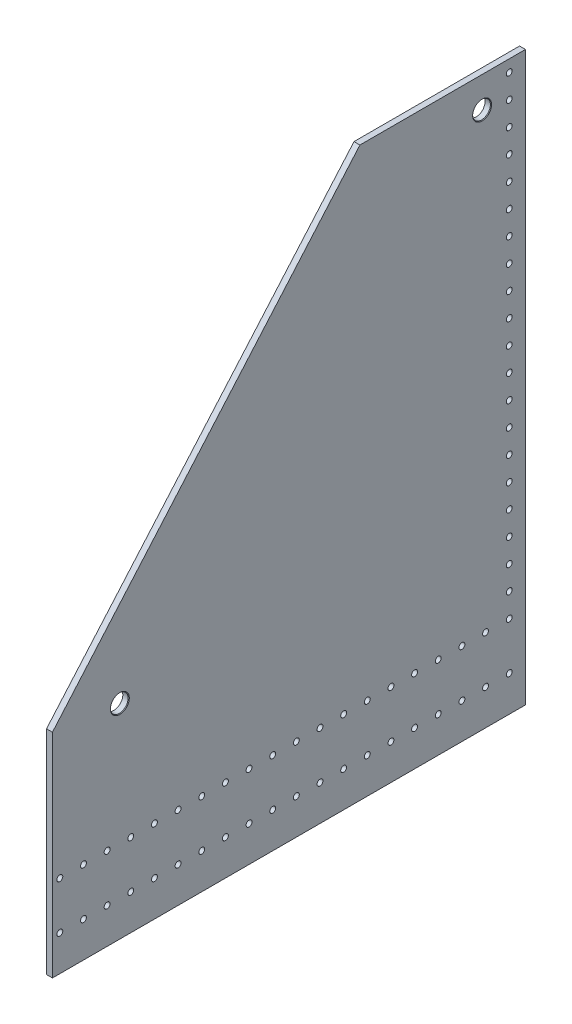
SolidWorks part; units mm, degrees
ref_plane "Front Plane" through (0, 0, 0) normal (0, 0, 1) x (1, 0, 0)
ref_plane "Top Plane" through (0, 0, 0) normal (0, 1, 0) x (1, 0, 0)
ref_plane "Right Plane" through (0, 0, 0) normal (1, 0, 0) x (0, 0, -1)
sketch "Sketch1" plane through (0, 0, 0) normal (1, 0, 0) x (0, 0, -1)
  line L1 (-86.4742, 48.8926) -> (421.5258, 48.8926)
  line L2 (-86.4742, 48.8926) -> (-86.4742, -560.7074)
  line L3 (-86.4742, -560.7074) -> (421.5258, -560.7074)
  line L4 (421.5258, 48.8926) -> (421.5258, -560.7074)
  dimension "D1" = 609.6
  dimension "D2" = 508
extrude "Boss-Extrude1" add sketch "Sketch1" along normal blind 6.35
sketch "Sketch4" plane through (6.35, 0, 0) normal (1, 0, 0) x (0, 0, -1)
  line L0 (-86.4742, 48.8926) -> (243.7258, 48.8926)
  line L1 (421.5258, 48.8926) -> (-86.4742, 48.8926) construction
  line L2 (243.7258, 48.8926) -> (-86.4742, -332.1074)
  line L3 (-86.4742, 48.8926) -> (-86.4742, -560.7074) construction
  line L4 (-86.4742, -332.1074) -> (-86.4742, 48.8926)
  dimension "D1" = 330.2
  dimension "D2" = 381
extrude "Cut-Extrude1" cut sketch "Sketch4" against normal blind 6.35
hole_wizard "3/4 (0.75) Diameter Hole1" positions "Sketch5" profile "Sketch6" hole size "3/4" standard "ANSI Inch" end condition through all
sketch "Sketch5" plane through (6.35, 0, 0) normal (1, 0, 0) x (0, 0, -1)
  point P0 (-14.0842, -341.6324)
  point P3 (374.9536, 15.7883)
sketch "Sketch6" plane through (6.35, -341.6324, 14.0842) normal (0, 1, 0) x (0, 0, -1)
  line L0 (0, 0) -> (0, 6.35)
  line L1 (0, 6.35) -> (9.525, 6.35)
  line L2 (9.525, 6.35) -> (9.525, 0.635)
  line L3 (9.525, 0.635) -> (10.16, 0)
  line L5 (10.16, 0) -> (0, 0)
  line L6 (-9.525, 0.635) -> (-10.16, 0) construction
  line L11 (0, -6.35) -> (0, 107.95) construction
  dimension "Thru Hole Dia." = 19.05
  dimension "Thru Hole Depth" = 6.35
  dimension "Near C'Sink Dia." = 20.32
  dimension "Near C'Sink Angle" = 90
hole_wizard "1/4 (0.25) Diameter Hole1" positions "Sketch7" profile "Sketch9" hole size "1/4" standard "ANSI Inch" end condition through all
sketch "Sketch7" plane through (6.35, 0, 0) normal (1, 0, 0) x (0, 0, -1)
  line L0 (-86.4742, -560.7074) -> (421.5258, -560.7074) construction
  line L1 (-86.4742, -332.1074) -> (-86.4742, -560.7074) construction
  point P0 (-78.5367, -522.6074)
  point P2 (-78.5367, -471.8074)
  point P18 (-53.1367, -522.6074)
  point P19 (-53.1367, -471.8074)
  point P20 (-27.7367, -522.6074)
  point P21 (-27.7367, -471.8074)
  point P22 (-2.3367, -522.6074)
  point P23 (-2.3367, -471.8074)
  point P24 (23.0633, -522.6074)
  point P25 (23.0633, -471.8074)
  point P26 (48.4633, -522.6074)
  point P27 (48.4633, -471.8074)
  point P28 (73.8633, -522.6074)
  point P29 (73.8633, -471.8074)
  point P30 (99.2633, -522.6074)
  point P31 (99.2633, -471.8074)
  point P32 (124.6633, -522.6074)
  point P33 (124.6633, -471.8074)
  point P34 (150.0633, -522.6074)
  point P35 (150.0633, -471.8074)
  point P36 (175.4633, -522.6074)
  point P37 (175.4633, -471.8074)
  point P38 (200.8633, -522.6074)
  point P39 (200.8633, -471.8074)
  point P40 (226.2633, -522.6074)
  point P41 (226.2633, -471.8074)
  point P42 (251.6633, -522.6074)
  point P43 (251.6633, -471.8074)
  point P44 (277.0633, -522.6074)
  point P45 (277.0633, -471.8074)
  point P46 (302.4633, -522.6074)
  point P47 (302.4633, -471.8074)
  point P48 (327.8633, -522.6074)
  point P49 (327.8633, -471.8074)
  point P50 (353.2633, -522.6074)
  point P51 (353.2633, -471.8074)
  point P52 (378.6633, -522.6074)
  point P53 (378.6633, -471.8074)
  point P54 (404.0633, -522.6074)
  point P55 (404.0633, -471.8074)
  dimension "D1" = 38.1
  dimension "D2" = 88.9
  dimension "D3" = 7.9375
  dimension "D4" = 7.9375
  dimension "D5" = 20
sketch "Sketch9" plane through (6.35, -522.6074, 78.5367) normal (0, 1, 0) x (0, 0, -1)
  line L0 (0, 0) -> (0, 6.35)
  line L1 (0, 6.35) -> (3.175, 6.35)
  line L2 (3.175, 6.35) -> (3.175, 0)
  line L5 (3.175, 0) -> (0, 0)
  line L11 (0, -6.35) -> (0, 107.95) construction
  dimension "Thru Hole Dia." = 6.35
  dimension "Thru Hole Depth" = 6.35
pattern_linear "LPattern2" count 21 spacing 25.4 along (0, 1, 0) of face at (0, -471.8074, -407.2383)
